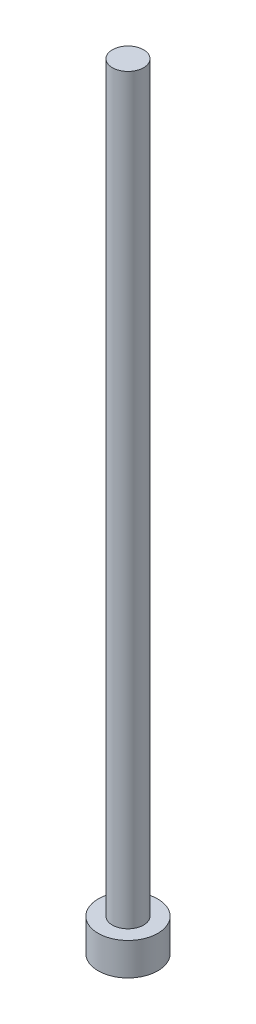
SolidWorks part; units mm, degrees
ref_plane "前视基准面" through (0, 0, 0) normal (0, 0, 1) x (1, 0, 0)
ref_plane "上视基准面" through (0, 0, 0) normal (0, 1, 0) x (1, 0, 0)
ref_plane "右视基准面" through (0, 0, 0) normal (1, 0, 0) x (0, 0, -1)
other "Configuration Table"
sketch "草图1" plane through (0, 0, 0) normal (0, 1, 0) x (1, 0, 0)
  line L1 (1.1547, 0) -> (0.5774, 1)
  line L2 (0.5774, 1) -> (-0.5774, 1)
  line L3 (-0.5774, 1) -> (-1.1547, 0)
  line L4 (-1.1547, 0) -> (-0.5774, -1)
  line L5 (-0.5774, -1) -> (0.5774, -1)
  line L6 (0.5774, -1) -> (1.1547, 0)
  circle A0 centre (0, 0) radius 1 construction
  circle A1 centre (0, 0) radius 2.2
  circle A2 centre (0, 0) radius 1.15
  point P11 (0, 0)
  dimension "D1" = 2
  dimension "D2" = 4.4
  dimension "D3" = 2.3
extrude "凸台-拉伸1" add sketch "草图1" along normal blind 2.4 contours A1
extrude "凸台-拉伸2" add sketch "草图1<4>" along normal blind 54.8 from surface contours A2 starting at face at (0, 2.4, 2.2)
sketch "草图1<4>" plane through (0, 0, 0) normal (0, 1, 0) x (1, 0, 0) same geometry as "草图1"
extrude "切除-拉伸1" cut sketch "草图1<3>" along normal blind 1.5 contours L5 A2 L6 L1 L2 L3 L4 region at (0, 0, 0)
sketch "草图1<3>" plane through (0, 0, 0) normal (0, 1, 0) x (1, 0, 0) same geometry as "草图1"
